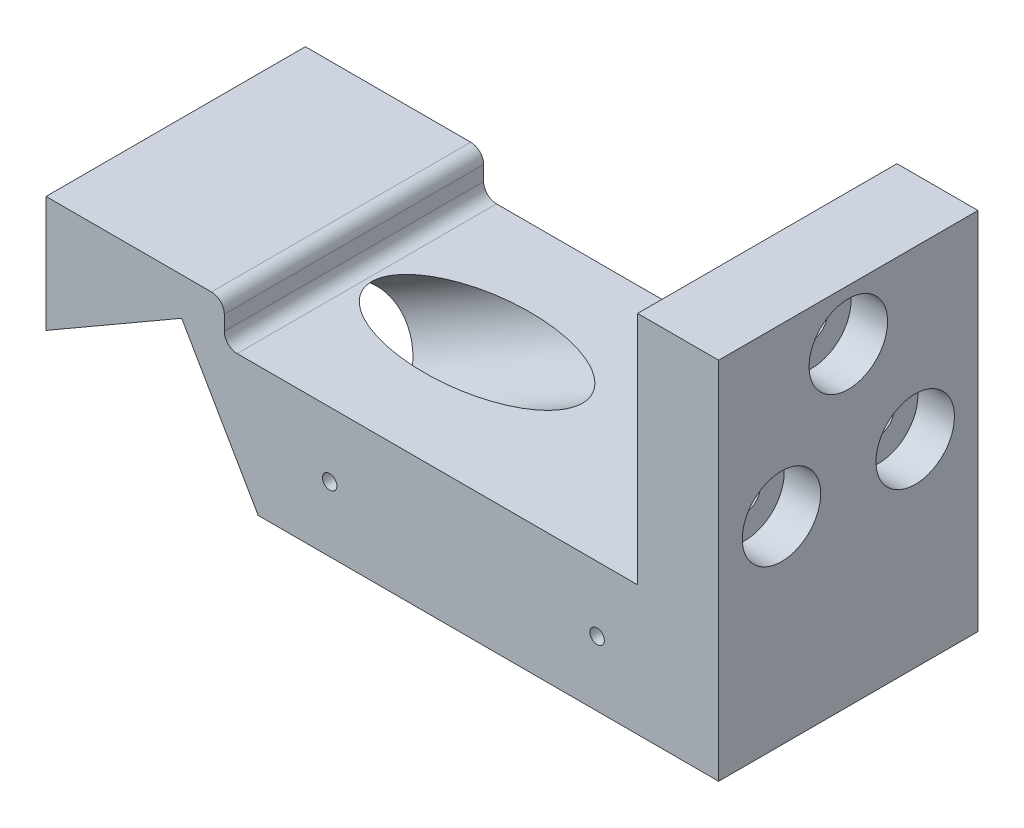
SolidWorks part; units mm, degrees
material "6061-T4 (SS)"
ref_plane "Front Plane" through (0, 0, 0) normal (0, 0, 1) x (1, 0, 0)
ref_plane "Top Plane" through (0, 0, 0) normal (0, 1, 0) x (1, 0, 0)
ref_plane "Right Plane" through (0, 0, 0) normal (1, 0, 0) x (0, 0, -1)
sketch "Sketch1" plane through (0, 0, 0) normal (0, 1, 0) x (1, 0, 0)
  line L1 (-36.5, 16) -> (36.5, 16)
  line L2 (-36.5, 16) -> (-36.5, -16)
  line L3 (-36.5, -16) -> (36.5, -16)
  line L4 (36.5, 16) -> (36.5, -16)
  line L5 (-36.5, 16) -> (36.5, -16) construction
  line L6 (-36.5, -16) -> (36.5, 16) construction
  point P0 (0, 0)
  dimension "D1" = 73
  dimension "D2" = 32
extrude "Boss-Extrude1" add sketch "Sketch1" along normal blind 16
sketch "Sketch78" plane through (0, 0, 16) normal (0, 0, 1) x (1, 0, 0)
  line L0 (-14.5, 16) -> (-12.9125, 16)
  line L1 (-36.5, 16) -> (-14.5, 16)
  line L2 (-36.5, 16) -> (-36.5, 21)
  line L3 (-36.5, 21) -> (-16.0875, 21)
  line L4 (-14.5, 17.5875) -> (-14.5, 19.4125)
  line L5 (-36.5, 16) -> (36.5, 16) construction
  line L6 (-12.9125, 16) -> (-12.9125, 17.5875) construction
  line L7 (-12.9125, 17.5875) -> (-14.5, 17.5875) construction
  arc A0 (-16.0875, 21) -> (-14.5, 19.4125) centre (-16.0875, 19.4125) cw
  arc A1 (-12.9125, 16) -> (-14.5, 17.5875) centre (-12.9125, 17.5875) cw
  dimension "D3" = 1.5875
  dimension "D1" = 5
  dimension "D2" = 22
  dimension "D4" = 1.5875
  dimension "D5" = 1.5875
extrude "Boss-Extrude4" add sketch "Sketch78" against normal up to surface (32 mm away) up to face at (0, 8, -16)
sketch "Sketch79" plane through (0, 0, -16) normal (0, 0, -1) x (-1, 0, 0)
  line L0 (-32.5, 1.97) -> (23.61, 1.97) construction
  line L1 (-32.5, 1.97) -> (-32.5, 29.2) construction
  line L2 (23.61, 1.97) -> (-20.8992, 27.6674) construction
  line L3 (33.135, 1.97) -> (34.135, 1.97) construction
  line L4 (14.4951, 7.2325) -> (19.7576, 16.3474)
  line L5 (19.7576, 16.3474) -> (36.5, 6.6812)
  line L6 (36.5, 21) -> (36.5, 0) construction
  line L7 (14.4951, 7.2325) -> (10.3194, 0)
  line L8 (-36.5, 0) -> (36.5, 0) construction
  line L9 (10.3194, 0) -> (36.5, 0)
  line L10 (36.5, 0) -> (36.5, 6.6812)
  circle A0 centre (23.61, 1.97) radius 9.525 construction
  circle A1 centre (23.61, 1.97) radius 10.525 construction
  dimension "D4" = 19.05
  dimension "D1" = 27.23
  dimension "D2" = 56.11
  dimension "D3" = 30
  dimension "D5" = 1
extrude "Cut-Extrude23" cut sketch "Sketch79" against normal blind 41
sketch "Sketch26" plane through (0, 0, 0) normal (0, -1, 0) x (1, 0, 0)
  line L0 (-10.3194, 16) -> (36.5, 16) construction
  line L1 (36.5, -16) -> (46.5, -16)
  line L2 (36.5, -16) -> (36.5, 16)
  line L3 (36.5, 16) -> (46.5, 16)
  line L4 (46.5, -16) -> (46.5, 16)
  dimension "D1" = 10
extrude "Boss-Extrude2" add sketch "Sketch26" against normal blind 45
sketch "Sketch15" plane through (-36.5, 0, 0) normal (-1, 0, 0) x (0, 0, 1)
  line L0 (-10, 14.6812) -> (10, 14.6812) construction
  line L1 (-10, 14.6812) -> (-16, 14.6812) construction
  line L3 (10, 14.6812) -> (16, 14.6812) construction
  line L6 (16, 21) -> (16, 6.6812) construction
  line L7 (-16, 21) -> (-16, 6.6812) construction
  line L9 (16, 6.6812) -> (-16, 6.6812) construction
  dimension "D3" = 20
  dimension "D4" = 8
sketch "Sketch14" plane through (-13.4261, 5.3809, -20) normal (-0.866, -0.5, 0) x (0, 0, 1)
  line L0 (4, 2.138) -> (20, 2.138) construction
  line L1 (20, 2.138) -> (36, 2.138) construction
  line L2 (36, 12.663) -> (36, -6.2133) construction
  line L3 (4, 12.663) -> (4, -6.2133) construction
  circle A0 centre (20, 2.138) radius 6.5
  dimension "D1" = 13
extrude "Cut-Extrude2" cut sketch "Sketch14" against normal blind 33 and the other way blind 41
sketch "Sketch27" plane through (46.5, 0, 0) normal (1, 0, 0) x (0, 0, -1)
  line L0 (16, 45) -> (-16, 45) construction
  line L1 (16, 45) -> (16, 0) construction
  line L3 (-8.2489, 24.4375) -> (8.2489, 24.4375) construction
  line L4 (0, 24.4375) -> (0, 38.725) construction
  line L5 (-8.2489, 24.4375) -> (-16, 24.4375) construction
  line L7 (8.2489, 24.4375) -> (16, 24.4375) construction
  line L9 (-16, 45) -> (-16, 0) construction
  circle A0 centre (0, 38.725) radius 1.595
  circle A1 centre (8.2489, 24.4375) radius 1.595
  circle A2 centre (-8.2489, 24.4375) radius 1.595
  dimension "D1" = 3.19
  dimension "D2" = 3.19
  dimension "D3" = 3.19
  dimension "D6" = 14.2875
  dimension "D7" = 16.4978
  dimension "D8" = 6.275
extrude "Cut-Extrude7" cut sketch "Sketch27" against normal through all
hole_wizard "#2-56 Tapped Hole1" positions "Sketch80" profile "Sketch81" tap size "#2-56" standard "ANSI Inch"
sketch "Sketch80" plane through (-36.5, 0, 0) normal (-1, 0, 0) x (0, 0, 1)
  point P0 (-10, 14.6812)
  point P3 (10, 14.6812)
sketch "Sketch81" plane through (-36.5, 14.6812, -10) normal (0, 1, 0) x (0, 0, 1)
  line L0 (0, 0) -> (0, 6.8842)
  line L1 (0, 6.8842) -> (0.889, 6.35)
  line L2 (0.889, 6.35) -> (0.889, 0)
  line L5 (0.889, 0) -> (0, 0)
  line L10 (0, 6.8842) -> (-0.889, 6.35) construction
  line L11 (0, -6.35) -> (0, 107.95) construction
  dimension "Tap Drill Dia." = 1.778
  dimension "Tap Drill Depth" = 6.35
  dimension "Drill Angle" = 118
hole_wizard "CBORE for #6 Socket Head Cap Screw1" positions "Sketch57" profile "Sketch58" counterbore size "#6" standard "ANSI Inch"
sketch "Sketch57" plane through (46.5, 0, 0) normal (1, 0, 0) x (0, 0, -1)
  point P0 (0, 38.725)
  point P3 (8.2489, 24.4375)
  point P6 (-8.2489, 24.4375)
sketch "Sketch58" plane through (46.5, 38.725, 0) normal (0, 1, 0) x (0, 0, -1)
  line L0 (0, 0) -> (0, 47.6408)
  line L1 (0, 47.6408) -> (1.8986, 46.5)
  line L2 (1.8986, 46.5) -> (1.8986, 4.5052)
  line L3 (1.8986, 4.5052) -> (4.8425, 4.5052)
  line L4 (4.8425, 4.5052) -> (4.8425, 0)
  line L5 (4.8425, 0) -> (0, 0)
  line L10 (0, 47.6408) -> (-1.8987, 46.5) construction
  line L11 (0, -6.35) -> (0, 107.95) construction
  dimension "Hole Dia." = 3.7973
  dimension "Hole Depth" = 46.5
  dimension "C'Bore Dia." = 9.685
  dimension "C'Bore Depth" = 4.5052
  dimension "Drill Angle" = 118
sketch "Sketch59" plane through (0, 0, -16) normal (0, 0, -1) x (-1, 0, 0)
  line L0 (36.5, 16) -> (36.5, 0) construction
  line L1 (36.5, 0) -> (-46.5, 0) construction
  line L2 (-46.5, 0) -> (-46.5, 16) construction
  line L3 (36.5, 21) -> (36.5, 6.6812) construction
  line L4 (-46.5, 16) -> (36.5, 16) construction
  line L5 (-46.5, 8) -> (36.5, 8) construction
  line L6 (-46.5, 45) -> (-46.5, 0) construction
  line L7 (-36.5, 16) -> (12.9125, 16) construction
  point P10 (-31.5, 8)
  point P11 (1.5, 8)
  dimension "D1" = 15
  dimension "D2" = 35
hole_wizard "#2-56 Tapped Hole2" positions "Sketch82" profile "Sketch83" tap size "#2-56" standard "ANSI Inch"
sketch "Sketch82" plane through (0, 0, -16) normal (0, 0, -1) x (-1, 0, 0)
  point P0 (-31.5, 8)
  point P3 (1.5, 8)
sketch "Sketch83" plane through (31.5, 8, -16) normal (1, 0, 0) x (0, 1, 0)
  line L0 (0, 0) -> (0, 6.8842)
  line L1 (0, 6.8842) -> (0.889, 6.35)
  line L2 (0.889, 6.35) -> (0.889, 0)
  line L5 (0.889, 0) -> (0, 0)
  line L10 (0, 6.8842) -> (-0.889, 6.35) construction
  line L11 (0, -6.35) -> (0, 107.95) construction
  dimension "Tap Drill Dia." = 1.778
  dimension "Tap Drill Depth" = 6.35
  dimension "Drill Angle" = 118
hole_wizard "#2-56 Tapped Hole3" positions "Sketch84" profile "Sketch85" tap size "#2-56" standard "ANSI Inch"
sketch "Sketch84" plane through (0, 0, 16) normal (0, 0, 1) x (1, 0, 0)
  point P0 (-1.5, 8)
  point P3 (31.5, 8)
sketch "Sketch85" plane through (-1.5, 8, 16) normal (1, 0, 0) x (0, -1, 0)
  line L0 (0, 0) -> (0, 6.8842)
  line L1 (0, 6.8842) -> (0.889, 6.35)
  line L2 (0.889, 6.35) -> (0.889, 0)
  line L5 (0.889, 0) -> (0, 0)
  line L10 (0, 6.8842) -> (-0.889, 6.35) construction
  line L11 (0, -6.35) -> (0, 107.95) construction
  dimension "Tap Drill Dia." = 1.778
  dimension "Tap Drill Depth" = 6.35
  dimension "Drill Angle" = 118
hole_wizard "#2-56 Tapped Hole4" positions "Sketch86" profile "Sketch87" tap size "#2-56" standard "ANSI Inch"
sketch "Sketch86" plane through (-7.7395, -4.4684, 0) normal (-0.866, -0.5, 0) x (0, 0, 1)
  line L0 (-10, 13.5111) -> (10, 13.5111) construction
  circle A1 centre (0, 13.5111) radius 6.5
  circle A2 centre (0, 13.5111) radius 6.5 construction
  point P0 (-10, 13.5111)
  point P2 (10, 13.5111)
  point P19 (0, 13.5111)
  dimension "D1" = 10
sketch "Sketch87" plane through (-14.4951, 7.2325, -10) normal (0, 0, 1) x (0.5, -0.866, 0)
  line L0 (0, 0) -> (0, 6.8842)
  line L1 (0, 6.8842) -> (0.889, 6.35)
  line L2 (0.889, 6.35) -> (0.889, 0)
  line L5 (0.889, 0) -> (0, 0)
  line L10 (0, 6.8842) -> (-0.889, 6.35) construction
  line L11 (0, -6.35) -> (0, 107.95) construction
  dimension "Tap Drill Dia." = 1.778
  dimension "Tap Drill Depth" = 6.35
  dimension "Drill Angle" = 118
sketch "Sketch88" plane through (46.5, 0, 0) normal (1, 0, 0) x (0, 0, -1)
  line L0 (-16, 45) -> (-16, 0) construction
  point P0 (-16, 22.5)
